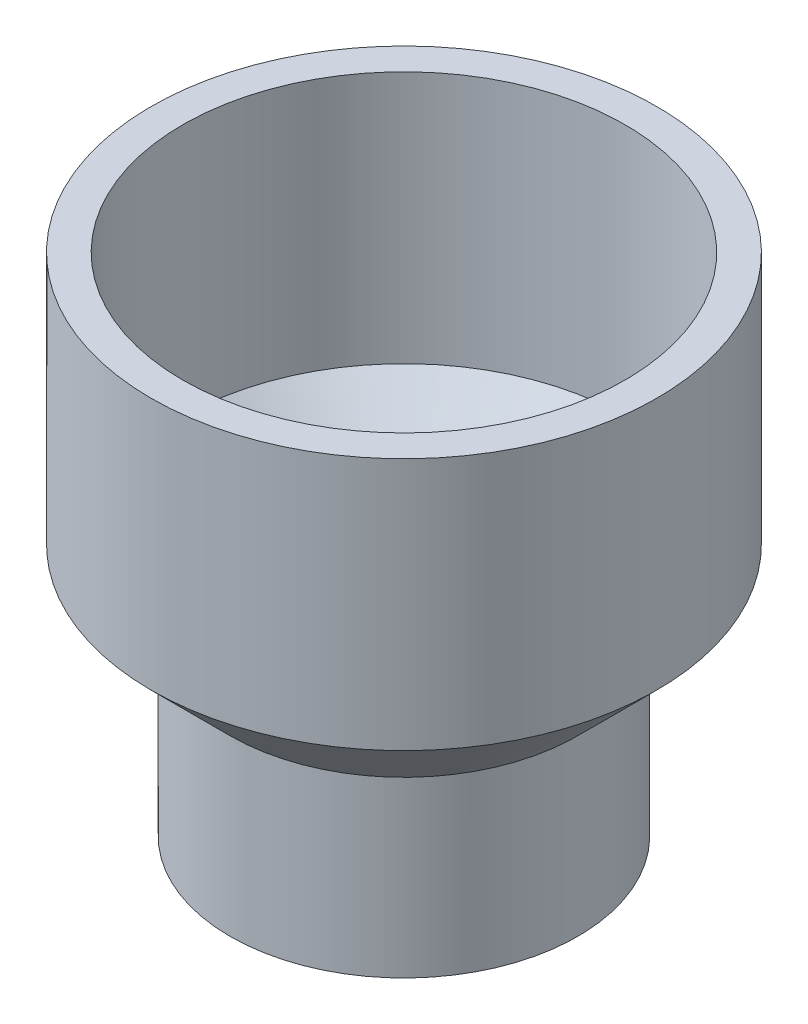
SolidWorks part; units mm, degrees
material "PVC Rigid"
ref_plane "Front Plane" through (0, 0, 0) normal (0, 0, 1) x (1, 0, 0)
ref_plane "Top Plane" through (0, 0, 0) normal (0, 1, 0) x (1, 0, 0)
ref_plane "Right Plane" through (0, 0, 0) normal (1, 0, 0) x (0, 0, -1)
sketch "Sketch1" plane through (0, 0, 0) normal (0, 1, 0) x (1, 0, 0)
  circle A0 centre (0, 0) radius 30.1625
  circle A1 centre (0, 0) radius 34.925
  dimension "D1" = 60.325
  dimension "D2" = 69.85
extrude "Boss-Extrude1" add sketch "Sketch1" along normal blind 50.8
sketch "Sketch2" plane through (0, 50.8, 0) normal (0, 1, 0) x (1, 0, 0)
  circle A0 centre (0, 0) radius 44.45
  circle A1 centre (0, 0) radius 50.8
  dimension "D1" = 88.9
  dimension "D2" = 6.35
extrude "Boss-Extrude2" add sketch "Sketch2" along normal blind 50.8 separate body
sketch "Sketch3" plane through (0, 0, 0) normal (0, 0, 1) x (1, 0, 0)
  line L0 (50.8, 50.8) -> (34.925, 34.925)
  line L1 (34.925, 0) -> (34.925, 50.8) construction
  line L2 (34.925, 34.925) -> (34.925, 50.8)
  line L3 (-50.8, 50.8) -> (50.8, 50.8) construction
  line L4 (34.925, 50.8) -> (50.8, 50.8)
ref_axis "Axis1" through (0, 101.6, 0) along (0, -1, 0)
revolve "Revolve1" add sketch "Sketch3" angle 360 about axis through (0, 101.6, 0) along (0, -1, 0)
sketch "Sketch4" plane through (0, 50.8, 0) normal (0, 1, 0) x (1, 0, 0)
  circle A0 centre (0, 0) radius 30.1625
  circle A1 centre (0, 0) radius 29.21
  circle A2 centre (0, 0) radius 30.1625 construction
  dimension "D1" = 58.42
extrude "Boss-Extrude3" add sketch "Sketch4" against normal offset from surface (15.0876 mm away) 35.7124 up to face at (0, 0, 34.925)
sketch "Sketch5" plane through (0, 0, 0) normal (1, 0, 0) x (0, 0, -1)
  line L0 (-44.45, 50.8) -> (-29.21, 36.195)
  line L1 (-50.8, 50.8) -> (50.8, 50.8) construction
  line L3 (-29.21, 36.195) -> (-29.21, 50.8)
  line L4 (-29.21, 50.8) -> (-44.45, 50.8)
  line L10 (-34.925, 34.925) -> (34.925, 34.925) construction
  dimension "D1" = 1.27
revolve "Cut-Revolve1" cut sketch "Sketch5" angle 360 about axis through (0, 101.6, 0) along (0, -1, 0)
ref_plane "Plane1" through (0, 50.8, 0) normal (0, -1, 0) x (-1, 0, 0)
sketch "Sketch6" plane through (0, 50.8, 0) normal (0, -1, 0) x (-1, 0, 0)
  line L0 (44.45, 0) -> (36.068, 0) construction
  circle A0 centre (0, 0) radius 44.45 construction
  circle A1 centre (36.068, 0) radius 2.2225
  dimension "D2" = 4.445
  dimension "D1" = 8.382
extrude "Cut-Extrude1" cut sketch "Sketch6" along normal up to surface (14.6636 mm away) up to face at (0, 50.8, 50.8)
ref_point "Point1"
ref_axis "Axis2" through (-36.068, 33.8455, 0) along (0, 1, 0)
ref_point "Point2"
ref_axis "Axis3" through (-36.068, 50.8, 0) along (1, 0, 0)
